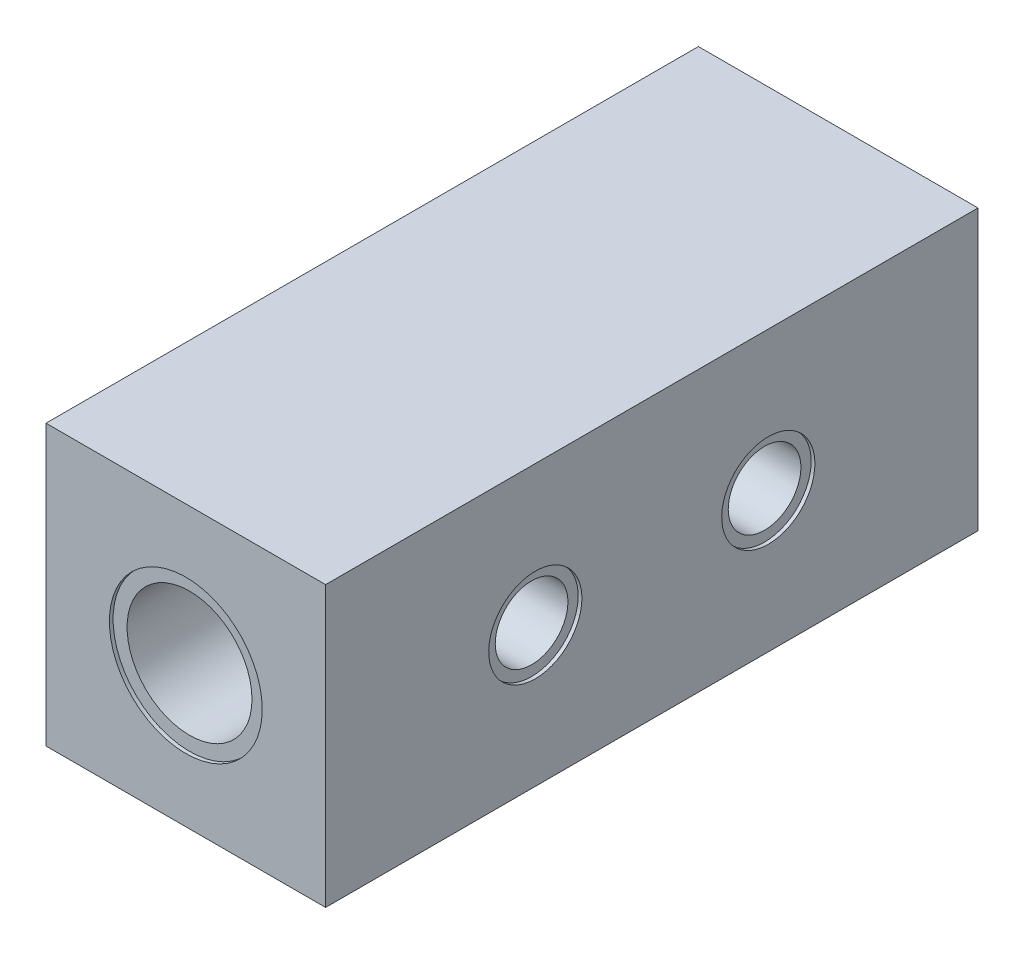
SolidWorks part; units mm, degrees
note: The reader was unsure of these and kept them because the rebuilt part matched: shared geometry of "Sketch13<2>", "Sketch14<3>", "Sketch14<4>".
material "AISI 316 Annealed Stainless Steel Bar (SS)"
ref_plane "Front Plane" through (0, 0, 0) normal (0, 0, 1) x (1, 0, 0)
ref_plane "Top Plane" through (0, 0, 0) normal (0, 1, 0) x (1, 0, 0)
ref_plane "Right Plane" through (0, 0, 0) normal (1, 0, 0) x (0, 0, -1)
sketch "Sketch1" plane through (0, 0, 0) normal (0, 0, 1) x (1, 0, 0)
  line L0 (0, 0) -> (0, -19.05) construction
  line L1 (-19.05, 19.05) -> (19.05, 19.05)
  line L2 (-19.05, 19.05) -> (-19.05, -19.05)
  line L3 (-19.05, -19.05) -> (19.05, -19.05)
  line L4 (19.05, 19.05) -> (19.05, -19.05)
  line L5 (0, 0) -> (-19.05, 0) construction
  circle A0 centre (0, 0) radius 8.509
  point P0 (0, 0)
  dimension "D3" = 17.018
  dimension "D1" = 38.1
  dimension "D2" = 38.1
  dimension "D4" = 19.05
extrude "Boss-Extrude1" add sketch "Sketch1" along normal mid plane 88.9
sketch "Sketch2" plane through (19.05, 0, 0) normal (1, 0, 0) x (0, 0, -1)
  line L0 (-44.45, 0) -> (-15.875, 0) construction
  line L1 (-44.45, -19.05) -> (-44.45, 19.05) construction
  line L2 (-15.875, 0) -> (15.875, 0) construction
  line L3 (44.45, -19.05) -> (44.45, 19.05) construction
  circle A0 centre (-15.875, 0) radius 4.953
  circle A1 centre (15.875, 0) radius 4.953
  dimension "D3" = 9.906
  dimension "D4" = 28.575
  dimension "D1" = 28.575
  dimension "D2" = 60.325
extrude "Cut-Extrude1" cut sketch "Sketch2" against normal through all
thread "Thread1" [suppressed] pitch 1.5875 start angle 0, offset 0, length 15.875, pitch 1.5875, diameter 17.018
ref_plane "Plane1" through (8.509, 0, -44.45) normal (0, -1, 0) x (1, 0, 0)
sketch "Thread Profile1" plane through (8.509, 0, -44.45) normal (0, -1, 0) x (1, 0, 0)
  line L0 (0, 0) -> (0, 1.5875) construction
  line L1 (0, 0) -> (0.8593, 0.4961)
  line L2 (0.8593, 0.4961) -> (0.8593, 0.6945)
  line L3 (0.8593, 0.6945) -> (0, 1.1906)
  line L4 (0.8593, 0.5953) -> (0, 0.5953) construction
  line L11 (0, 0) -> (0, 1.1906)
  point P2 (0, 0)
  dimension "Pitch" = 1.5875
  dimension "Profile_Angle" = 60
  dimension "Profile_Land" = 0.1984
  dimension "Profile_Height" = 0.8593
thread "Thread3" [suppressed] pitch 1.27 start angle 0, offset 0, length 11.43, pitch 1.27, diameter 9.906
ref_plane "Plane3" through (-19.05, 0, -20.828) normal (0, -1, 0) x (0, 0, -1)
sketch "Thread Profile3" plane through (-19.05, 0, -20.828) normal (0, -1, 0) x (0, 0, -1)
  line L0 (0, 0) -> (0, 1.27) construction
  line L1 (0, 0) -> (0.6874, 0.3969)
  line L2 (0.6874, 0.3969) -> (0.6874, 0.5556)
  line L3 (0.6874, 0.5556) -> (0, 0.9525)
  line L4 (0.6874, 0.4762) -> (0, 0.4762) construction
  line L11 (0, 0) -> (0, 0.9525)
  point P2 (0, 0)
  dimension "Pitch" = 1.27
  dimension "Profile_Angle" = 60
  dimension "Profile_Land" = 0.1588
  dimension "Profile_Height" = 0.6874
thread "Thread4" [suppressed] pitch 1.27 start angle 0, offset 0, length 11.43, pitch 1.27, diameter 9.906
ref_plane "Plane4" through (-19.05, 0, 10.922) normal (0, -1, 0) x (0, 0, -1)
sketch "Thread Profile4" plane through (-19.05, 0, 10.922) normal (0, -1, 0) x (0, 0, -1)
  line L0 (0, 0) -> (0, 1.27) construction
  line L1 (0, 0) -> (0.6874, 0.3969)
  line L2 (0.6874, 0.3969) -> (0.6874, 0.5556)
  line L3 (0.6874, 0.5556) -> (0, 0.9525)
  line L4 (0.6874, 0.4762) -> (0, 0.4762) construction
  line L11 (0, 0) -> (0, 0.9525)
  point P2 (0, 0)
  dimension "Pitch" = 1.27
  dimension "Profile_Angle" = 60
  dimension "Profile_Land" = 0.1588
  dimension "Profile_Height" = 0.6874
thread "Thread5" [suppressed] pitch 1.27 start angle 0, offset 0, length 11.43, pitch 1.27, diameter 9.906
ref_plane "Plane5" through (19.05, 0, -10.922) normal (0, -1, 0) x (0, 0, 1)
sketch "Thread Profile5" plane through (19.05, 0, -10.922) normal (0, -1, 0) x (0, 0, 1)
  line L0 (0, 0) -> (0, 1.27) construction
  line L1 (0, 0) -> (0.6874, 0.3969)
  line L2 (0.6874, 0.3969) -> (0.6874, 0.5556)
  line L3 (0.6874, 0.5556) -> (0, 0.9525)
  line L4 (0.6874, 0.4762) -> (0, 0.4762) construction
  line L11 (0, 0) -> (0, 0.9525)
  point P2 (0, 0)
  dimension "Pitch" = 1.27
  dimension "Profile_Angle" = 60
  dimension "Profile_Land" = 0.1588
  dimension "Profile_Height" = 0.6874
thread "Thread6" [suppressed] pitch 1.27 start angle 0, offset 0, length 11.43, pitch 1.27, diameter 9.906
ref_plane "Plane6" through (19.05, 0, 20.828) normal (0, -1, 0) x (0, 0, 1)
sketch "Thread Profile6" plane through (19.05, 0, 20.828) normal (0, -1, 0) x (0, 0, 1)
  line L0 (0, 0) -> (0, 1.27) construction
  line L1 (0, 0) -> (0.6874, 0.3969)
  line L2 (0.6874, 0.3969) -> (0.6874, 0.5556)
  line L3 (0.6874, 0.5556) -> (0, 0.9525)
  line L4 (0.6874, 0.4762) -> (0, 0.4762) construction
  line L11 (0, 0) -> (0, 0.9525)
  point P2 (0, 0)
  dimension "Pitch" = 1.27
  dimension "Profile_Angle" = 60
  dimension "Profile_Land" = 0.1588
  dimension "Profile_Height" = 0.6874
thread "Thread7" [suppressed] pitch 1.5875 start angle 0, offset 0, length 15.875, pitch 1.5875, diameter 17.018
ref_plane "Plane7" through (-8.509, 0, 44.45) normal (0, -1, 0) x (-1, 0, 0)
sketch "Thread Profile7" plane through (-8.509, 0, 44.45) normal (0, -1, 0) x (-1, 0, 0)
  line L0 (0, 0) -> (0, 1.5875) construction
  line L1 (0, 0) -> (0.8593, 0.4961)
  line L2 (0.8593, 0.4961) -> (0.8593, 0.6945)
  line L3 (0.8593, 0.6945) -> (0, 1.1906)
  line L4 (0.8593, 0.5953) -> (0, 0.5953) construction
  line L11 (0, 0) -> (0, 1.1906)
  point P2 (0, 0)
  dimension "Pitch" = 1.5875
  dimension "Profile_Angle" = 60
  dimension "Profile_Land" = 0.1984
  dimension "Profile_Height" = 0.8593
sketch "Sketch13" plane through (0, 0, 0) normal (0, 0, 1) x (1, 0, 0)
  circle A0 centre (0, 0) radius 10.414
  dimension "D1" = 20.828
extrude "Cut-Extrude2" cut sketch "Sketch13" against normal blind 0.508 from surface at 44.45 starting at face at (0, 0, 44.45)
extrude "Cut-Extrude3" cut sketch "Sketch13<2>" along normal blind 0.508 from surface at -44.45 starting at face at (0, 0, -44.45)
sketch "Sketch13<2>" plane through (0, 0, 0) normal (0, 0, 1) x (1, 0, 0) same geometry as "Sketch13"
sketch "Sketch14" plane through (0, 0, 0) normal (1, 0, 0) x (0, 0, -1)
  circle A0 centre (-15.875, 0) radius 6.35
  circle A1 centre (15.875, 0) radius 6.35
  dimension "D1" = 12.7
  dimension "D2" = 12.7
extrude "Cut-Extrude4" cut sketch "Sketch14" against normal blind 0.508 from surface at 19.05 contours A0 starting at face at (19.05, 4.953, 15.875)
extrude "Cut-Extrude5" cut sketch "Sketch14<3>" against normal blind 0.508 from surface at 19.05 starting at face at (19.05, -6.35, 15.875)
sketch "Sketch14<3>" plane through (0, 0, 0) normal (1, 0, 0) x (0, 0, -1) same geometry as "Sketch14"
extrude "Cut-Extrude6" cut sketch "Sketch14<4>" along normal blind 0.508 from surface at -19.05 starting at face at (-19.05, 4.953, 15.875)
sketch "Sketch14<4>" plane through (0, 0, 0) normal (1, 0, 0) x (0, 0, -1) same geometry as "Sketch14"
